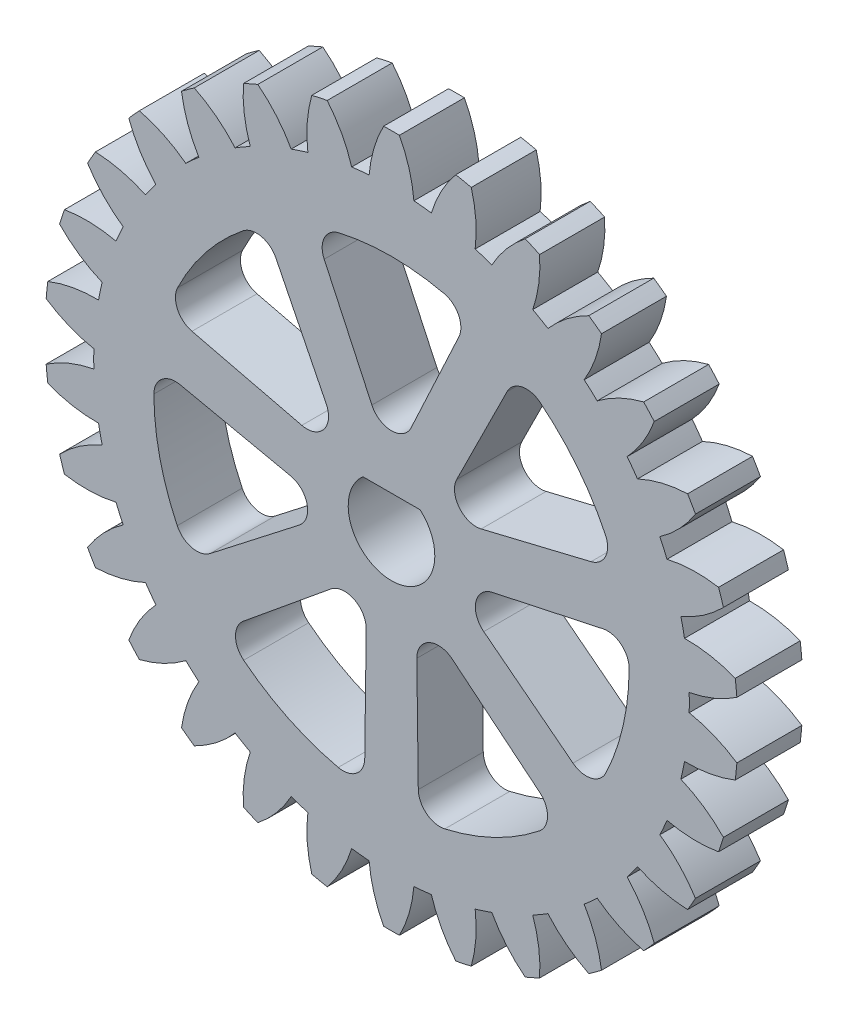
SolidWorks part; units mm, degrees
ref_plane "Front Plane" through (0, 0, 0) normal (0, 0, 1) x (1, 0, 0)
ref_plane "Top Plane" through (0, 0, 0) normal (0, 1, 0) x (1, 0, 0)
ref_plane "Right Plane" through (0, 0, 0) normal (1, 0, 0) x (0, 0, -1)
sketch "Sketch1" plane through (0, 0, 0) normal (0, 0, 1) x (1, 0, 0)
  circle A0 centre (0, 0) radius 16
  dimension "D1" = 32
extrude "Boss-Extrude1" add sketch "Sketch1" along normal blind 3
sketch "Sketch2" plane through (0, 0, 0) normal (0, 0, -1) x (-1, 0, 0)
  line L0 (0, 0) -> (0, 31.1786) construction
  line L1 (0, 0) -> (3.3147, 31.5373) construction
  line L2 (0.7854, 14.9794) -> (0, 14.9794) construction
  circle A0 centre (0, 0) radius 13.75 construction
  circle A1 centre (0, 0) radius 14.0954 construction
  circle A2 centre (0, 0) radius 15 construction
  arc A3 (1.0336, 13.7111) -> (1.8397, 13.6264) centre (0, 0) cw
  arc A4 (1.0336, 13.7111) -> (0.364, 15.9959) centre (-4.9446, 13.1997) ccw
  circle A5 centre (0, 0) radius 16 construction
  arc A6 (1.8397, 13.6264) -> (2.9696, 15.722) centre (7.5809, 11.8832) cw
  arc A7 (0.364, 15.9959) -> (2.9696, 15.722) centre (0, 0) cw
  dimension "D3" = 30
  dimension "D1" = 27.5
  dimension "D5" = 6
  dimension "D2" = 28.1908
  dimension "D4" = 6
  dimension "D6" = 0.7854
extrude "Cut-Extrude1" cut sketch "Sketch2" against normal through all
pattern_circular "CirPattern1" count 30 over 360 about axis through (0, 0, 0) along (0, 0, 1) of "Cut-Extrude1"
sketch "Sketch4" plane through (0, 0, 0) normal (0, 0, -1) x (-1, 0, 0)
  line L0 (0, 2.6286) -> (3.6024, 10.3643)
  line L1 (0, 2.6286) -> (-3.6024, 10.3643)
  line L2 (0, 0) -> (0, 10.9725) construction
  arc A1 (-3.6024, 10.3643) -> (3.6024, 10.3643) centre (0, 0) cw
  circle A2 centre (0, 0) radius 2.6286 construction
  dimension "D1" = 8.5333
extrude "Cut-Extrude3" cut sketch "Sketch4" against normal through all
fillet "Fillet6" radius 1 3 edges at (0, 2.6286, 1.5) (-3.6024, 10.3643, 1.5) (3.6024, 10.3643, 1.5)
pattern_circular "CirPattern3" count 7 over 360 about axis through (0, 0, 0) along (0, 0, 1) of "Fillet6", "Cut-Extrude3"
sketch "Sketch5" plane through (0, 0, 0) normal (0, 0, -1) x (-1, 0, 0)
  line L1 (-1.3229, 1.5) -> (1.3229, 1.5)
  arc A1 (-1.3229, 1.5) -> (1.3229, 1.5) centre (0, 0) ccw
  dimension "D1" = 1.5
  dimension "D2" = 2
extrude "Cut-Extrude4" cut sketch "Sketch5" against normal blind 10
equation "\"module\" = 1.0"
equation "\"teeth\"= 30"
equation "\"pressureAngle\"= 20deg"
equation "\"gearThickness\"= 3"
equation "\"addendumFactor\"= 1"
equation "\"dedendumFactor\"= 1.25"
equation "\"pitch\"= 1 / \"module\""
equation "\"pitchDiameter\"= \"teeth\" / \"pitch\""
equation "\"addendum\"= \"addendumFactor\" / \"pitch\""
equation "\"dedendum\"= \"dedendumFactor\" / \"pitch\""
equation "\"D1@Boss-Extrude1\"=\"gearThickness\""
equation "\"D4@Sketch2\"=180/\"teeth\""
equation "\"D3@Sketch2\"=\"pitchDiameter\""
equation "\"D1@Sketch2\"=\"pitchDiameter\"-2*\"dedendum\""
equation "\"D5@Sketch2\"=\"pitchDiameter\"/5"
equation "\"D6@Sketch2\"=pi/2/\"pitch\"/2"
equation "\"D1@Sketch1\"=\"pitchDiameter\"+2*\"addendum\""
equation "\"D2@Sketch2\"=\"pitchDiameter\" * cos ( \"pressureAngle\" )"
equation "\"D1@CirPattern1\"=\"teeth\""
equation "\"D1@Sketch4\"= (\"pitchDiameter\" + 2 * \"addendum\")/3.75"
